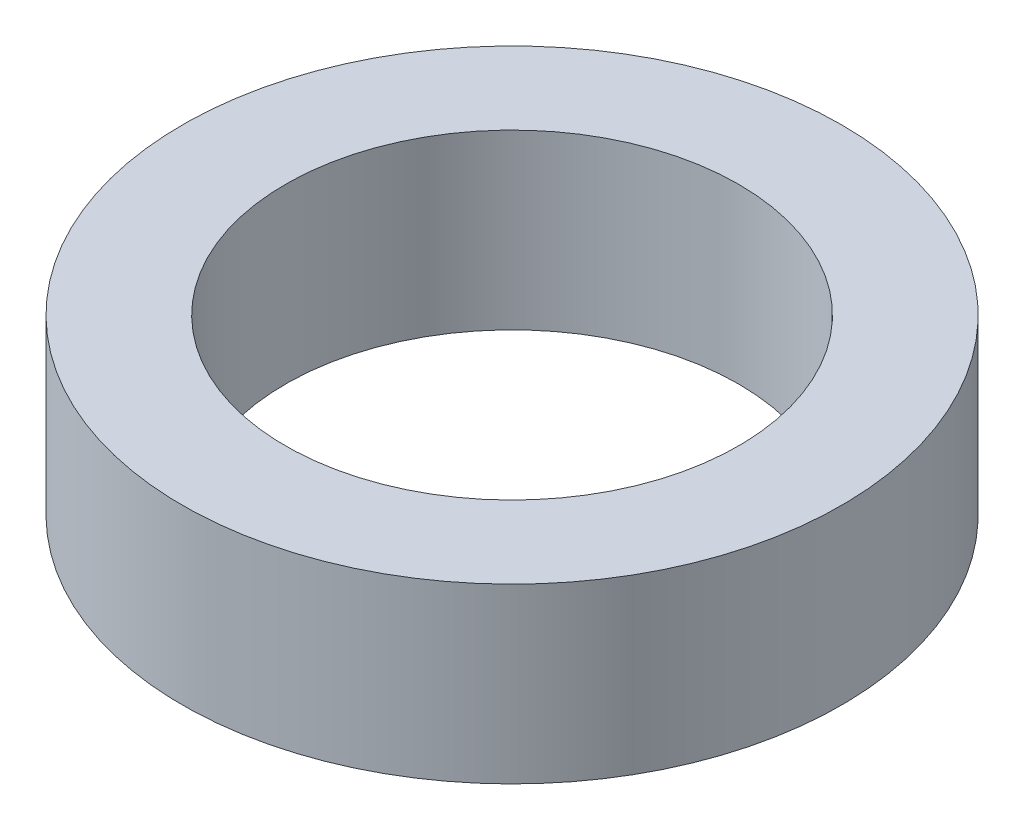
SolidWorks part; units mm, degrees
ref_plane "Front Plane" through (0, 0, 0) normal (0, 0, 1) x (1, 0, 0)
ref_plane "Top Plane" through (0, 0, 0) normal (0, 1, 0) x (1, 0, 0)
ref_plane "Right Plane" through (0, 0, 0) normal (1, 0, 0) x (0, 0, -1)
sketch "Sketch1" plane through (0, 0, 0) normal (0, 1, 0) x (1, 0, 0)
  circle A0 centre (0, 0) radius 40
  dimension "FLANGE_OD" = 80
extrude "Boss-Extrude1" add sketch "Sketch1" along normal blind 21
sketch "Sketch2" plane through (0, 0, 0) normal (0, 1, 0) x (1, 0, 0)
  circle A0 centre (0, 0) radius 27.5
  dimension "BORE_D" = 55
extrude "Cut-Extrude1" cut sketch "Sketch2" along normal through all
sketch "Sketch3" plane through (0, 21, 0) normal (0, 1, 0) x (1, 0, 0)
  circle A0 centre (0, 0) radius 18.0902 construction
  circle A1 centre (-18.0902, 0) radius 1.9682
  dimension "BOLT_D" = 3.9364
  dimension "BOLT_PCD" = 36.1805
extrude "Cut-Extrude2" cut sketch "Sketch3" against normal blind 18.3933 rebuild error yes
pattern_circular "CirPattern1" count 4 over 360 rebuild error yes
